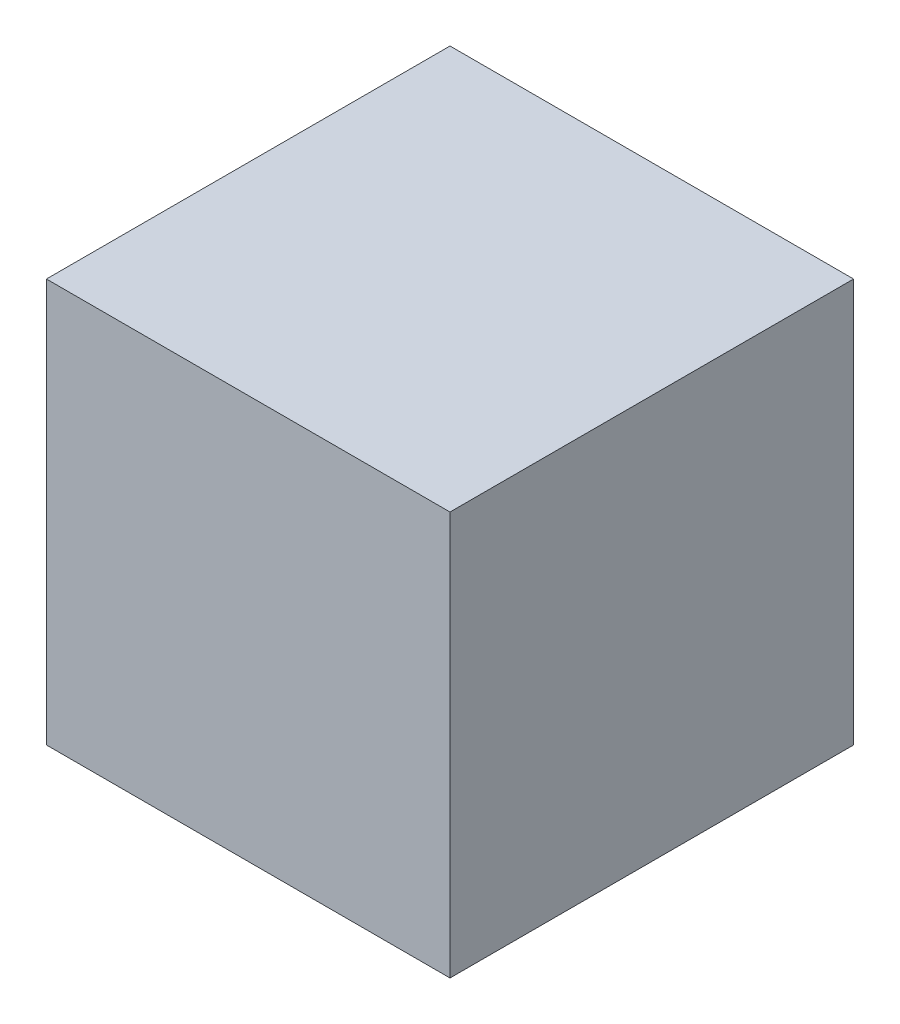
SolidWorks part; units mm, degrees
ref_plane "Спереди" through (0, 0, 0) normal (0, 0, 1) x (1, 0, 0)
ref_plane "Сверху" through (0, 0, 0) normal (0, 1, 0) x (1, 0, 0)
ref_plane "Справа" through (0, 0, 0) normal (1, 0, 0) x (0, 0, -1)
sketch "Эскиз1" plane through (0, 0, 0) normal (0, 1, 0) x (1, 0, 0)
  line L1 (0, 0) -> (250, 0)
  line L2 (0, 0) -> (0, 250)
  line L3 (0, 250) -> (250, 250)
  line L4 (250, 0) -> (250, 250)
  dimension "D1" = 250
  dimension "D2" = 250
extrude "Бобышка-Вытянуть1" add sketch "Эскиз1" along normal blind 250
